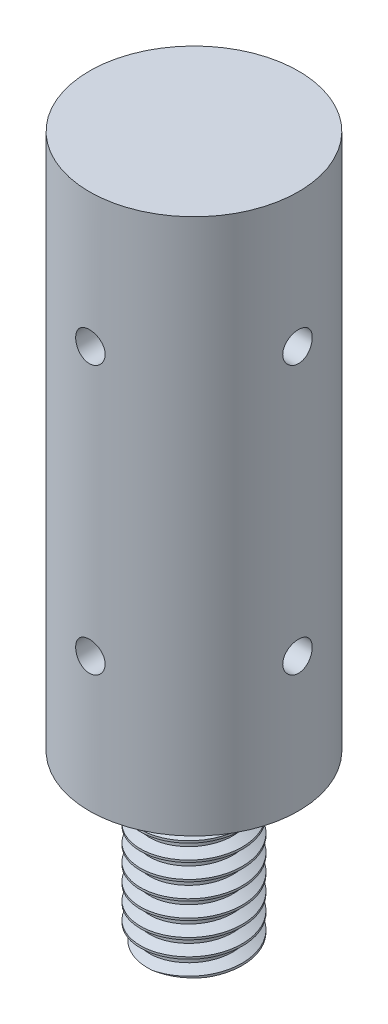
SolidWorks part; units mm, degrees
ref_plane "Front Plane" through (0, 0, 0) normal (0, 0, 1) x (1, 0, 0)
ref_plane "Top Plane" through (0, 0, 0) normal (0, 1, 0) x (1, 0, 0)
ref_plane "Right Plane" through (0, 0, 0) normal (1, 0, 0) x (0, 0, -1)
sketch "Sketch1" plane through (0, 0, 0) normal (0, 1, 0) x (1, 0, 0)
  circle A0 centre (0, 0) radius 4.953
  dimension "D1" = 9.906
extrude "Boss-Extrude1" add sketch "Sketch1" along normal blind 25.4
sketch "Sketch2" plane through (0, 0, 0) normal (0, -1, 0) x (1, 0, 0)
  circle A0 centre (0, 0) radius 2.413
  dimension "D1" = 4.826
extrude "Boss-Extrude2" add sketch "Sketch2" along normal blind 7.62
thread "Thread2" pitch 0.7937 method cut profile "Thread Profile2" start angle 0, offset 0, length 0, pitch 0.7937, diameter 4.826
ref_plane "Plane2" through (-2.413, 0, 0) normal (0, 0, 1) x (-1, 0, 0)
sketch "Thread Profile2" plane through (-2.413, 0, 0) normal (0, 0, 1) x (-1, 0, 0)
  line L0 (0, 0) -> (0, 0.7937) construction
  line L11 (0, 0) -> (0, 0.6945)
  line L12 (0, 0.6945) -> (-0.4296, 0.4465)
  line L13 (-0.4296, 0.4465) -> (-0.4296, 0.248)
  line L15 (-0.4296, 0.248) -> (0, 0)
  line L17 (-0.4296, 0.3473) -> (0, 0.3473) construction
  point P2 (0, 0)
  dimension "Pitch" = 0.7937
  dimension "Profile_Angle" = 60
  dimension "Profile_Land" = 0.1984
  dimension "Profile_Height" = 0.4296
ref_plane "Plane3" through (-4.953, 0, 0) normal (-1, 0, 0) x (0, 0, 1)
sketch "Sketch8" plane through (-4.953, 0, 0) normal (-1, 0, 0) x (0, 0, 1)
  line L0 (0, 0) -> (0, 25.4) construction
  circle A0 centre (0, 6.35) radius 0.6985
  circle A1 centre (0, 19.05) radius 0.6985
  dimension "D2" = 1.397
  dimension "D3" = 1.397
  dimension "D1" = 25.4
  dimension "D4" = 12.7
  dimension "D5" = 6.35
extrude "Cut-Extrude1" cut sketch "Sketch8" against normal blind 3.175
pattern_circular "CirPattern1" count 4 over 360 about axis through (0, 25.4, 0) along (0, 1, 0) of "Cut-Extrude1"
